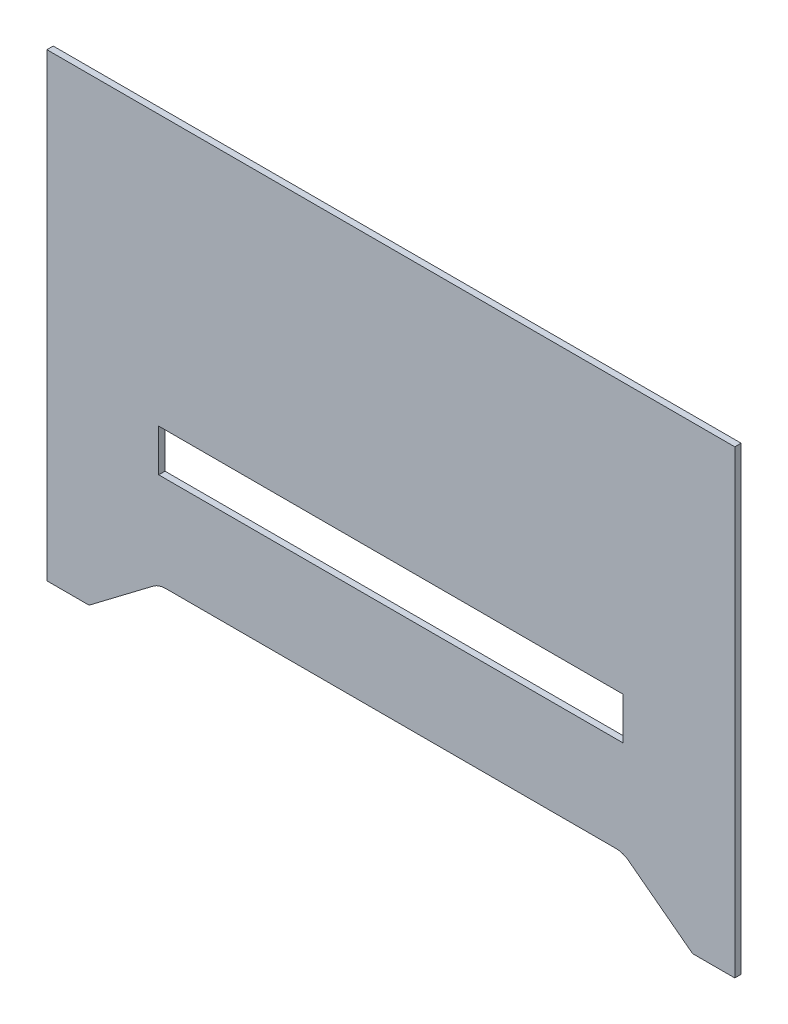
SolidWorks part; units mm, degrees
ref_plane "前视基准面" through (0, 0, 0) normal (0, 0, 1) x (1, 0, 0)
ref_plane "上视基准面" through (0, 0, 0) normal (0, 1, 0) x (1, 0, 0)
ref_plane "右视基准面" through (0, 0, 0) normal (1, 0, 0) x (0, 0, -1)
sketch "Sketch1" plane through (0, 0, 0) normal (0, 0, 1) x (1, 0, 0)
  line L0 (0, -109) -> (0, 0) construction
  line L1 (-163, -109) -> (163, -109) construction
  line L2 (-163, -109) -> (-163, 109)
  line L3 (-163, 109) -> (163, 109)
  line L4 (163, -109) -> (163, 109)
  line L5 (-163, -109) -> (163, 109) construction
  line L6 (-163, 109) -> (163, -109) construction
  line L7 (-106.6398, -84) -> (106.6398, -84)
  line L8 (112.6784, -86.0291) -> (143, -109)
  line L9 (143, -109) -> (163, -109)
  line L10 (-143, -109) -> (-163, -109)
  line L11 (-112.6784, -86.0291) -> (-143, -109)
  line L13 (-110, -39) -> (110, -39)
  line L14 (-110, -39) -> (-110, -19)
  line L15 (-110, -19) -> (110, -19)
  line L16 (110, -39) -> (110, -19)
  line L17 (-110, -39) -> (110, -19) construction
  line L18 (-110, -19) -> (110, -39) construction
  arc A0 (112.6784, -86.0291) -> (106.6398, -84) centre (106.6398, -94) ccw
  arc A1 (-112.6784, -86.0291) -> (-106.6398, -84) centre (-106.6398, -94) cw
  point P0 (0, 0)
  point P8 (0, -29)
  point P13 (110, -84)
  point P18 (0, -84)
  dimension "D6" = 10
  dimension "D1" = 326
  dimension "D2" = 218
  dimension "D3" = 25
  dimension "D4" = 20
  dimension "D5" = 110
  dimension "D7" = 220
  dimension "D8" = 20
  dimension "D9" = 128
extrude "Boss-Extrude1" add sketch "Sketch1" along normal blind 3
